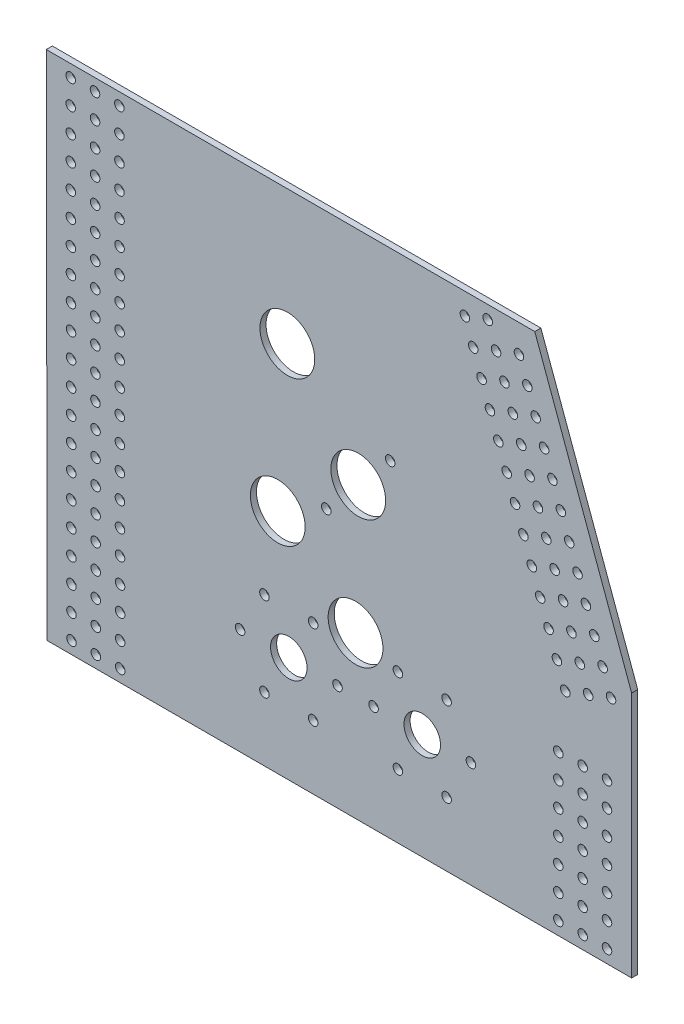
SolidWorks part; units mm, degrees
ref_plane "Front Plane" through (0, 0, 0) normal (0, 0, 1) x (1, 0, 0)
ref_plane "Top Plane" through (0, 0, 0) normal (0, 1, 0) x (1, 0, 0)
ref_plane "Right Plane" through (0, 0, 0) normal (1, 0, 0) x (0, 0, -1)
sketch "Sketch1" plane through (0, 0, 0) normal (0, 0, 1) x (1, 0, 0)
  line B0 (-0.0251, 266.6996) -> (254.7308, 266.6996)
  line B1 (0.4372, 0) -> (-0.0251, 266.6996)
  line B2 (0.4372, 0) -> (305.2377, 0)
  line B3 (305.2377, 0) -> (305.2377, 128.6779)
  line B4 (305.2377, 128.6779) -> (254.7308, 266.6996)
  circle B5 centre (25.3859, 260.3496) radius 2.4892
  circle B6 centre (38.0859, 260.3496) radius 2.4892
  circle B7 centre (25.4079, 247.6496) radius 2.4892
  circle B8 centre (125.6826, 196.681) radius 14.2875
  circle B9 centre (162.6718, 151.4627) radius 14.2875
  circle B10 centre (120.691, 118.5613) radius 14.2875
  circle B11 centre (161.2509, 83.907) radius 14.2875
  circle B12 centre (38.1079, 247.6496) radius 2.4892
  circle B13 centre (12.6859, 260.3496) radius 2.4892
  circle B14 centre (25.4299, 234.9497) radius 2.4892
  circle B15 centre (38.1299, 234.9497) radius 2.4892
  circle B16 centre (25.452, 222.2497) radius 2.4892
  circle B17 centre (38.152, 222.2497) radius 2.4892
  circle B18 centre (25.474, 209.5497) radius 2.4892
  circle B19 centre (38.174, 209.5497) radius 2.4892
  circle B20 centre (25.496, 196.8497) radius 2.4892
  circle B21 centre (38.196, 196.8497) radius 2.4892
  circle B22 centre (25.518, 184.1497) radius 2.4892
  circle B23 centre (38.218, 184.1497) radius 2.4892
  circle B24 centre (25.54, 171.4498) radius 2.4892
  circle B25 centre (38.24, 171.4498) radius 2.4892
  circle B26 centre (25.562, 158.7498) radius 2.4892
  circle B27 centre (38.262, 158.7498) radius 2.4892
  circle B28 centre (25.5841, 146.0498) radius 2.4892
  circle B29 centre (38.2841, 146.0498) radius 2.4892
  circle B30 centre (25.6061, 133.3498) radius 2.4892
  circle B31 centre (38.3061, 133.3498) radius 2.4892
  circle B32 centre (25.6281, 120.6498) radius 2.4892
  circle B33 centre (38.3281, 120.6498) radius 2.4892
  circle B34 centre (25.6501, 107.9498) radius 2.4892
  circle B35 centre (38.3501, 107.9498) radius 2.4892
  circle B36 centre (25.6721, 95.2499) radius 2.4892
  circle B37 centre (38.3721, 95.2499) radius 2.4892
  circle B38 centre (25.6941, 82.5499) radius 2.4892
  circle B39 centre (38.3941, 82.5499) radius 2.4892
  circle B40 centre (25.7162, 69.8499) radius 2.4892
  circle B41 centre (38.4162, 69.8499) radius 2.4892
  circle B42 centre (25.7382, 57.1499) radius 2.4892
  circle B43 centre (38.4382, 57.1499) radius 2.4892
  circle B44 centre (25.7602, 44.4499) radius 2.4892
  circle B45 centre (38.4602, 44.4499) radius 2.4892
  circle B46 centre (25.7822, 31.75) radius 2.4892
  circle B47 centre (38.4822, 31.75) radius 2.4892
  circle B48 centre (25.8042, 19.05) radius 2.4892
  circle B49 centre (38.5042, 19.05) radius 2.4892
  circle B50 centre (25.8262, 6.35) radius 2.4892
  circle B51 centre (38.5262, 6.35) radius 2.4892
  circle B52 centre (12.7079, 247.6496) radius 2.4892
  circle B53 centre (12.7299, 234.9497) radius 2.4892
  circle B54 centre (12.752, 222.2497) radius 2.4892
  circle B55 centre (12.774, 209.5497) radius 2.4892
  circle B56 centre (12.796, 196.8497) radius 2.4892
  circle B57 centre (12.818, 184.1497) radius 2.4892
  circle B58 centre (12.84, 171.4498) radius 2.4892
  circle B59 centre (12.862, 158.7498) radius 2.4892
  circle B60 centre (12.8841, 146.0498) radius 2.4892
  circle B61 centre (12.9061, 133.3498) radius 2.4892
  circle B62 centre (12.9281, 120.6498) radius 2.4892
  circle B63 centre (12.9501, 107.9498) radius 2.4892
  circle B64 centre (12.9721, 95.2499) radius 2.4892
  circle B65 centre (12.9941, 82.5499) radius 2.4892
  circle B66 centre (13.0162, 69.8499) radius 2.4892
  circle B67 centre (13.0382, 57.1499) radius 2.4892
  circle B68 centre (13.0602, 44.4499) radius 2.4892
  circle B69 centre (13.0822, 31.75) radius 2.4892
  circle B70 centre (13.1042, 19.05) radius 2.4892
  circle B71 centre (13.1262, 6.35) radius 2.4892
  circle B72 centre (218.2671, 255.4759) radius 2.4892
  circle B73 centre (222.6314, 243.5493) radius 2.4892
  circle B74 centre (226.9958, 231.6228) radius 2.4892
  circle B75 centre (231.3601, 219.6962) radius 2.4892
  circle B76 centre (235.7244, 207.7697) radius 2.4892
  circle B77 centre (240.0888, 195.8431) radius 2.4892
  circle B78 centre (244.4531, 183.9166) radius 2.4892
  circle B79 centre (248.8175, 171.99) radius 2.4892
  circle B80 centre (253.1818, 160.0635) radius 2.4892
  circle B81 centre (257.5461, 148.1369) radius 2.4892
  circle B82 centre (261.9105, 136.2104) radius 2.4892
  circle B83 centre (266.2748, 124.2838) radius 2.4892
  circle B84 centre (270.6391, 112.3573) radius 2.4892
  circle B85 centre (230.1936, 259.8402) radius 2.4892
  circle B86 centre (246.4845, 252.278) radius 2.4892
  circle B87 centre (234.558, 247.9137) radius 2.4892
  circle B88 centre (238.9223, 235.9871) radius 2.4892
  circle B89 centre (243.2867, 224.0606) radius 2.4892
  circle B90 centre (247.651, 212.134) radius 2.4892
  circle B91 centre (252.0153, 200.2075) radius 2.4892
  circle B92 centre (256.3797, 188.2809) radius 2.4892
  circle B93 centre (260.744, 176.3544) radius 2.4892
  circle B94 centre (265.1083, 164.4278) radius 2.4892
  circle B95 centre (269.4727, 152.5013) radius 2.4892
  circle B96 centre (273.837, 140.5747) radius 2.4892
  circle B97 centre (278.2014, 128.6482) radius 2.4892
  circle B98 centre (282.5657, 116.7216) radius 2.4892
  circle B99 centre (250.8489, 240.3514) radius 2.4892
  circle B100 centre (255.2132, 228.4249) radius 2.4892
  circle B101 centre (259.5775, 216.4984) radius 2.4892
  circle B102 centre (263.9419, 204.5718) radius 2.4892
  circle B103 centre (268.3062, 192.6453) radius 2.4892
  circle B104 centre (272.6706, 180.7187) radius 2.4892
  circle B105 centre (277.0349, 168.7922) radius 2.4892
  circle B106 centre (281.3992, 156.8656) radius 2.4892
  circle B107 centre (285.7636, 144.9391) radius 2.4892
  circle B108 centre (290.1279, 133.0125) radius 2.4892
  circle B109 centre (294.4922, 121.086) radius 2.4892
  circle B110 centre (266.9938, 82.9902) radius 2.4892
  circle B111 centre (279.6938, 82.9902) radius 2.4892
  circle B112 centre (292.3938, 82.9902) radius 2.4892
  circle B113 centre (279.6938, 70.2902) radius 2.4892
  circle B114 centre (292.3938, 70.2902) radius 2.4892
  circle B115 centre (279.6938, 57.5902) radius 2.4892
  circle B116 centre (292.3938, 57.5902) radius 2.4892
  circle B117 centre (279.6938, 44.8902) radius 2.4892
  circle B118 centre (292.3938, 44.8902) radius 2.4892
  circle B119 centre (279.6938, 32.1902) radius 2.4892
  circle B120 centre (292.3938, 32.1902) radius 2.4892
  circle B121 centre (279.6938, 19.4902) radius 2.4892
  circle B122 centre (292.3938, 19.4902) radius 2.4892
  circle B123 centre (279.6938, 6.7902) radius 2.4892
  circle B124 centre (292.3938, 6.7902) radius 2.4892
  circle B125 centre (266.9938, 70.2902) radius 2.4892
  circle B126 centre (266.9938, 57.5902) radius 2.4892
  circle B127 centre (266.9938, 44.8902) radius 2.4892
  circle B128 centre (266.9938, 32.1902) radius 2.4892
  circle B129 centre (266.9938, 19.4902) radius 2.4892
  circle B130 centre (266.9938, 6.7902) radius 2.4892
  circle B131 centre (196.0489, 55.3411) radius 9.525
  circle B132 centre (126.4529, 55.3411) radius 9.525
  circle B133 centre (221.4489, 55.3411) radius 2.4892
  circle B134 centre (208.7489, 33.3441) radius 2.4892
  circle B135 centre (183.3489, 33.3441) radius 2.4892
  circle B136 centre (170.6489, 55.3411) radius 2.4892
  circle B137 centre (183.3489, 77.3382) radius 2.4892
  circle B138 centre (208.7489, 77.3382) radius 2.4892
  circle B139 centre (101.0529, 55.3411) radius 2.4892
  circle B140 centre (113.7529, 77.3382) radius 2.4892
  circle B141 centre (139.1529, 77.3382) radius 2.4892
  circle B142 centre (151.8529, 55.3411) radius 2.4892
  circle B143 centre (139.1529, 33.3441) radius 2.4892
  circle B144 centre (113.7529, 33.3441) radius 2.4892
  circle B145 centre (179.3164, 170.656) radius 2.4892
  circle B146 centre (146.0134, 132.2952) radius 2.4892
sketch_block_instance "Block-Plate1-1"
sketch_block "Block-Plate1" parameters "D1"=28.575, "D2"=28.575, "D3"=28.575, "D4"=28.575, "D8"=4.9784, "D12"=4.9784, "D16"=19.05, "D17"=19.05, "D18"=4.9784, "D22"=4.9784, "D24"=4.9784, "D25"=4.9784, "D5"=12.7, "D6"=12.7, "D7"=12.7, "D9"=12.7, "D10"=12.7, "D11"=12.7, "D13"=12.7, "D14"=12.7, "D15"=6.7902, "D19"=25.4, "D20"=25.4, "D21"=25.4, "D23"=25.4
extrude "Boss-Extrude1" add sketch "Sketch1" along normal blind 3.175
